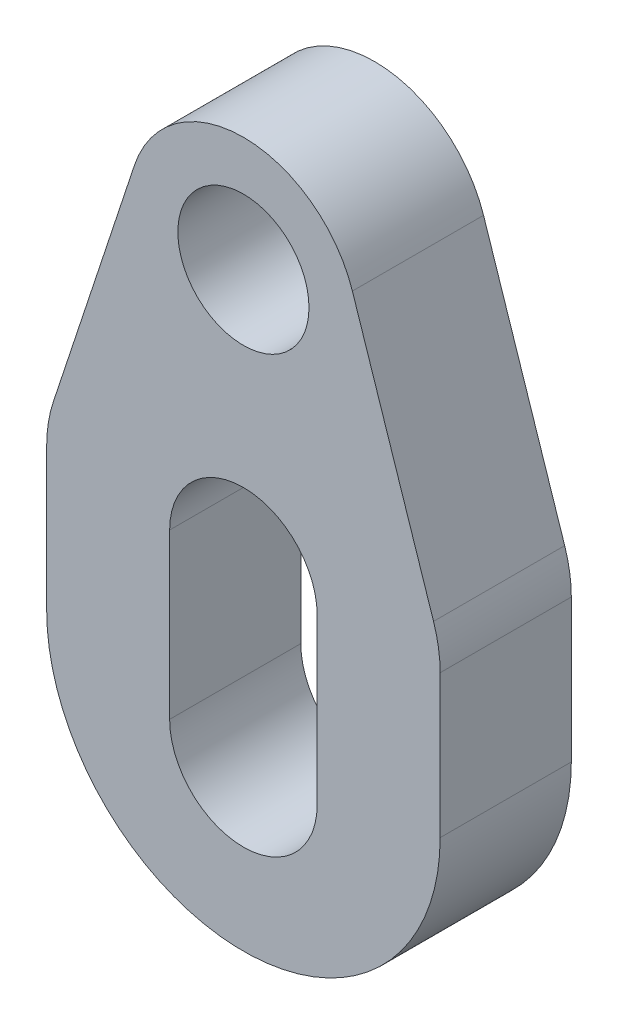
SolidWorks part; units mm, degrees
material "SS 304 (Default)"
ref_plane "Front Plane" through (0, 0, 0) normal (0, 0, 1) x (1, 0, 0)
ref_plane "Top Plane" through (0, 0, 0) normal (0, 1, 0) x (1, 0, 0)
ref_plane "Right Plane" through (0, 0, 0) normal (1, 0, 0) x (0, 0, -1)
sketch "Sketch1" plane through (0, 0, 0) normal (0, 0, 1) x (1, 0, 0)
  line L0 (0, 7.9375) -> (0, -7.9375) construction
  line L1 (9.525, 7.9375) -> (9.525, -7.9375)
  line L2 (-9.525, 7.9375) -> (-9.525, -7.9375)
  arc A0 (9.525, 7.9375) -> (-9.525, 7.9375) centre (0, 7.9375) ccw
  arc A1 (-9.525, -7.9375) -> (9.525, -7.9375) centre (0, -7.9375) ccw
  point P2 (0, 0)
  dimension "D1" = 9.525
  dimension "D2" = 15.875
sheet metal parameters "Sheet-Metal1" thickness 6.35 parameters "D1"=8.7312
base flange "Base-Flange1" sketch "Sketch1" thickness 6.35 reverse thickness direction yes parameters "D1"=8.7312
hole_wizard "1/4 (0.25) Diameter Hole1" positions "Sketch2" profile "Sketch3" hole size "1/4" standard "ANSI Inch" end condition up to next
sketch "Sketch2" plane through (0, 0, 6.35) normal (0, 0, 1) x (1, 0, 0)
  arc A0 (9.525, 7.9375) -> (-9.525, 7.9375) centre (0, 7.9375) ccw construction
  point P0 (0, 11.1125)
  dimension "D1" = 3.175
sketch "Sketch3" plane through (0, 11.1125, 6.35) normal (1, 0, 0) x (0, -1, 0)
  line L0 (0, 0) -> (0, 6.35)
  line L1 (0, 6.35) -> (3.175, 6.35)
  line L2 (3.175, 6.35) -> (3.175, 0)
  line L5 (3.175, 0) -> (0, 0)
  line L11 (0, -6.35) -> (0, 107.95) construction
  dimension "Thru Hole Dia." = 6.35
  dimension "Thru Hole Depth" = 6.35
hole_wizard "9/32 (0.28125) Diameter Hole1" positions "Sketch4" profile "Sketch5" hole size "9/32" standard "ANSI Inch" end condition up to next
sketch "Sketch4" plane through (0, 0, 6.35) normal (0, 0, 1) x (1, 0, 0)
  arc A0 (-9.525, -7.9375) -> (9.525, -7.9375) centre (0, -7.9375) ccw construction
  point P0 (0, -9.525)
  point P9 (0, -17.4625)
  dimension "D1" = 7.9375
sketch "Sketch5" plane through (0, -9.525, 6.35) normal (1, 0, 0) x (0, -1, 0)
  line L0 (0, 0) -> (0, 6.35)
  line L1 (0, 6.35) -> (3.5719, 6.35)
  line L2 (3.5719, 6.35) -> (3.5719, 0)
  line L5 (3.5719, 0) -> (0, 0)
  line L11 (0, -6.35) -> (0, 107.95) construction
  dimension "Thru Hole Dia." = 7.1437
  dimension "Thru Hole Depth" = 6.35
sketch "Sketch6" plane through (0, 0, 6.35) normal (0, 0, 1) x (1, 0, 0)
  line L0 (0, -9.525) -> (0, -1.5875) construction
  line L1 (-3.5719, -9.525) -> (-3.5719, -1.5875)
  line L2 (3.5719, -9.525) -> (3.5719, -1.5875)
  arc A0 (-3.5719, -9.525) -> (3.5719, -9.525) centre (0, -9.525) ccw
  arc A1 (3.5719, -1.5875) -> (-3.5719, -1.5875) centre (0, -1.5875) ccw
  circle A2 centre (0, -9.525) radius 3.5719 construction
  circle A3 centre (0, 11.1125) radius 3.175 construction
  point P4 (0, -5.5562)
  dimension "D1" = 12.7
extrude "Cut-Extrude1" cut sketch "Sketch6" against normal up to next normal cut yes
sketch "Sketch7" plane through (0, 0, 6.35) normal (0, 0, 1) x (1, 0, 0)
  line L0 (-9.525, 0) -> (-4.3368, 16.4179)
  line L1 (-9.525, 7.9375) -> (-9.525, -7.9375) construction
  line L2 (-4.3368, 16.4179) -> (4.3368, 16.4179)
  line L3 (4.3368, 16.4179) -> (9.525, 0)
  line L4 (9.525, -7.9375) -> (9.525, 7.9375) construction
  line L5 (9.525, 0) -> (9.525, 17.4625)
  line L6 (9.525, 17.4625) -> (-9.525, 17.4625)
  line L7 (-9.525, 17.4625) -> (-9.525, 0)
  line L8 (-9.525, 0) -> (-5.2755, 12.8563)
  line L9 (-5.2755, 12.8563) -> (5.2755, 12.8563)
  line L10 (5.2755, 12.8563) -> (9.525, 0)
  arc A0 (9.525, 7.9375) -> (-9.525, 7.9375) centre (0, 7.9375) ccw construction
  circle A1 centre (0, 11.1125) radius 5.5562
  arc M6 (9.525, 7.9375) -> (-9.525, 7.9375) centre (0, 7.9375) ccw
  line M7 (-9.525, 7.9375) -> (-9.525, -7.9375)
  line M9 (9.525, -7.9375) -> (9.525, 7.9375)
  dimension "D1" = 11.1125
extrude "Cut-Extrude2" cut sketch "Sketch7" against normal through all contours A1 L2 L0 L8 | A1 L10 L3 L2 | L3 M6 M9 | L0 M7 M6 | A1 L2 M6 region at (-7.6751, 9.4853, 6.35) region at (-6.9136, 8.2035, 6.35) region at (0, 16.8697, 6.35) region at (4.0217, 15.2057, 6.35) region at (7.6751, 9.4853, 6.35) normal cut yes
fillet "Fillet1" radius 6.35 2 edges at (9.525, 0, 3.175) (-9.525, 0, 3.175)
flat pattern "Flat-Pattern1" [suppressed]
sketch "Bend-Lines1" plane through (0, 0, 0) normal (0, 1, 0) x (-1, 0, 0)
sketch3d "Bounding-Box1" [suppressed]
  line L0 (9.525, 9.5249, 0) -> (9.525, -25.3999, 0) construction
  line L1 (-9.525, 9.5249, 0) -> (-9.525, -25.3999, 0) construction
  line L2 (9.525, 9.5249, 0) -> (-9.525, 9.5249, 0) construction
  line L3 (9.525, -25.3999, 0) -> (-9.525, -25.3999, 0) construction
